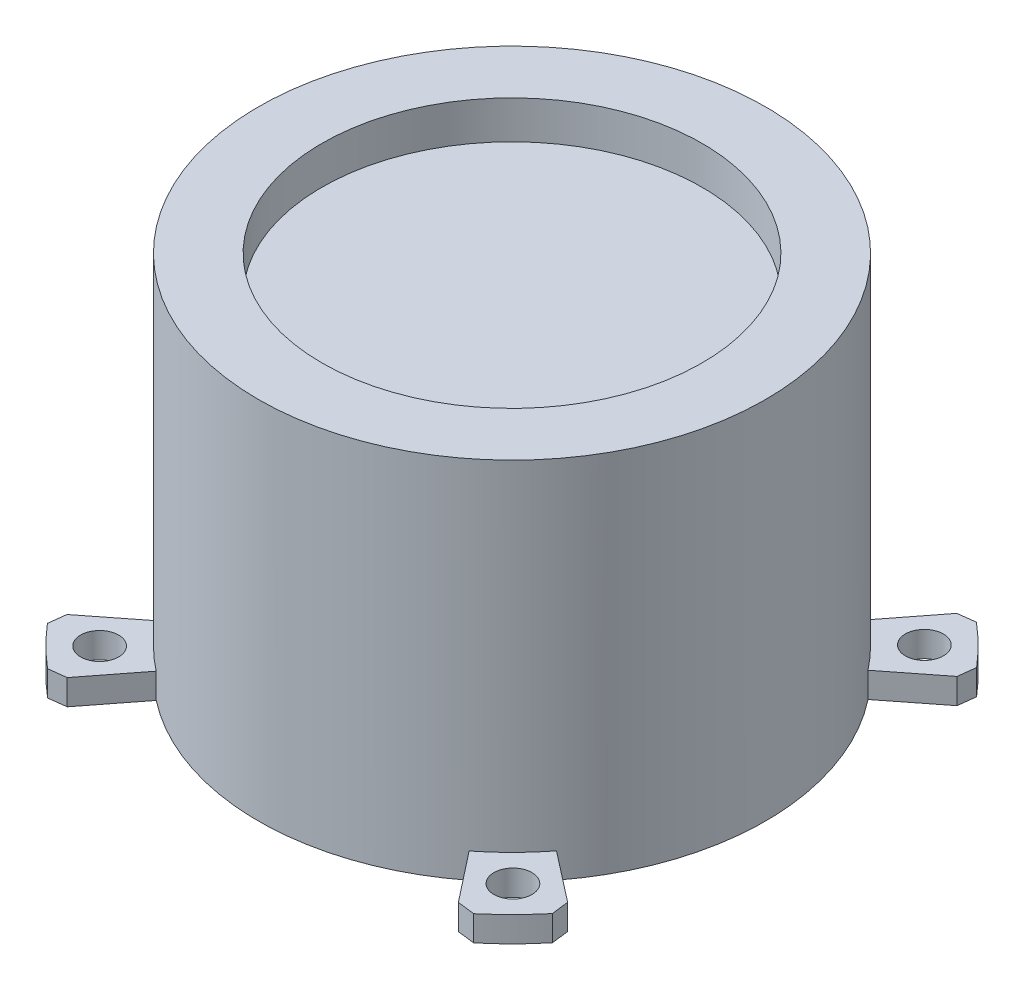
SolidWorks part; units mm, degrees
ref_plane "Front Plane" through (0, 0, 0) normal (0, 0, 1) x (1, 0, 0)
ref_plane "Top Plane" through (0, 0, 0) normal (0, 1, 0) x (1, 0, 0)
ref_plane "Right Plane" through (0, 0, 0) normal (1, 0, 0) x (0, 0, -1)
sketch "Sketch1" plane through (0, 0, 0) normal (0, 1, 0) x (1, 0, 0)
  circle A0 centre (0, 0) radius 20
  dimension "D1" = 40
extrude "Boss-Extrude1" add sketch "Sketch1" along normal blind 25.8
sketch "Sketch2" plane through (0, 0, 0) normal (0, 1, 0) x (1, 0, 0)
  line L0 (-12.3487, 15.7325) -> (-16.0533, 20.4522)
  line L3 (-14.1739, 14.1103) -> (-18.4261, 18.3434) construction
  line L10 (-15.7879, 12.2777) -> (-20.5243, 15.961)
  line L11 (15.7325, 12.3487) -> (20.4522, 16.0533)
  line L12 (12.2777, 15.7879) -> (15.961, 20.5243)
  line L13 (12.3487, -15.7325) -> (16.0533, -20.4522)
  line L14 (15.7879, -12.2777) -> (20.5243, -15.961)
  line L15 (-15.7325, -12.3487) -> (-20.4522, -16.0533)
  line L16 (-12.2777, -15.7879) -> (-15.961, -20.5243)
  arc A8 (-12.3487, 15.7325) -> (-15.7879, 12.2777) centre (0, 0) ccw
  arc A9 (-16.0533, 20.4522) -> (-20.5243, 15.961) centre (0, 0) ccw
  circle A10 centre (-16.3, 16.2268) radius 1.5
  arc A11 (20.4522, 16.0533) -> (15.961, 20.5243) centre (0, 0) ccw
  arc A12 (15.7325, 12.3487) -> (12.2777, 15.7879) centre (0, 0) ccw
  circle A13 centre (16.2268, 16.3) radius 1.5
  arc A14 (16.0533, -20.4522) -> (20.5243, -15.961) centre (0, 0) ccw
  arc A15 (12.3487, -15.7325) -> (15.7879, -12.2777) centre (0, 0) ccw
  circle A16 centre (16.3, -16.2268) radius 1.5
  arc A17 (-20.4522, -16.0533) -> (-15.961, -20.5243) centre (0, 0) ccw
  arc A18 (-15.7325, -12.3487) -> (-12.2777, -15.7879) centre (0, 0) ccw
  circle A19 centre (-16.2268, -16.3) radius 1.5
  point P24 (0, 0)
  point P31 (0, 0)
  dimension "D1" = 52
  dimension "D3" = 3
  dimension "D2" = 14
  dimension "D4" = 4
extrude "Boss-Extrude4" add sketch "Sketch2" along normal blind 2
chamfer "Chamfer1" distance 1 angle 45 8 edges at (15.961, 1, -20.5243) (20.4522, 1, -16.0533) (-16.0533, 1, -20.4522) (-20.5243, 1, -15.961) (-20.4522, 1, 16.0533) (-15.961, 1, 20.5243) (20.5243, 1, 15.961) (16.0533, 1, 20.4522)
sketch "Sketch3" plane through (0, 25.8, 0) normal (0, 1, 0) x (1, 0, 0)
  circle A0 centre (0, 0) radius 20
  circle A1 centre (0, 0) radius 15
  dimension "D1" = 30
extrude "Boss-Extrude5" add sketch "Sketch3" along normal blind 3
